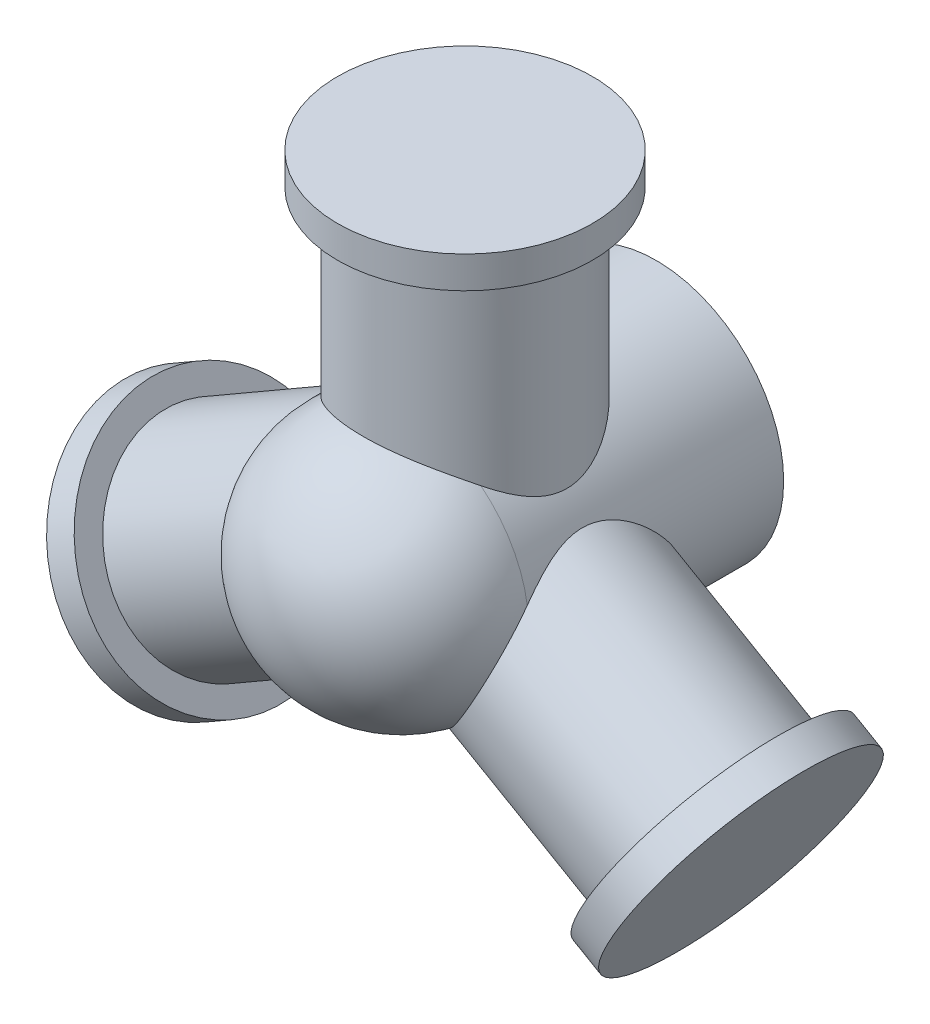
SolidWorks part; units mm, degrees
ref_plane "Ebene vorne" through (0, 0, 0) normal (0, 0, 1) x (1, 0, 0)
ref_plane "Ebene oben" through (0, 0, 0) normal (0, 1, 0) x (1, 0, 0)
ref_plane "Ebene rechts" through (0, 0, 0) normal (1, 0, 0) x (0, 0, -1)
sketch "Skizze1" plane through (0, 0, 0) normal (0, 0, 1) x (1, 0, 0)
  circle A0 centre (0, 0) radius 2000
extrude "Aufsatz-Linear austragen1" add sketch "Skizze1" along normal blind 3000 and the other way blind 3000
sketch "Skizze2" plane through (0, 0, 0) normal (0, 1, 0) x (1, 0, 0)
  circle A0 centre (0, 0) radius 1600
extrude "Aufsatz-Linear austragen2" add sketch "Skizze2" along normal blind 5000
sketch "Skizze3" plane through (0, 0, 0) normal (0, 1, 0) x (1, 0, 0)
  circle A0 centre (0, 0) radius 2000
extrude "Aufsatz-Linear austragen3" add sketch "Skizze3" along normal blind 500 from offset 4500
pattern_circular "Kreismuster1" count 3 over 360 about axis through (0, 0, -3000) along (0, 0, -1) of "Aufsatz-Linear austragen2" reverse direction yes
pattern_circular "Kreismuster2" count 3 over 360 about axis through (0, 0, -3000) along (0, 0, -1) of "Aufsatz-Linear austragen3" reverse direction yes
fillet "Verrundung1" radius 2000 1 edges at (2000, 0, 3000)
